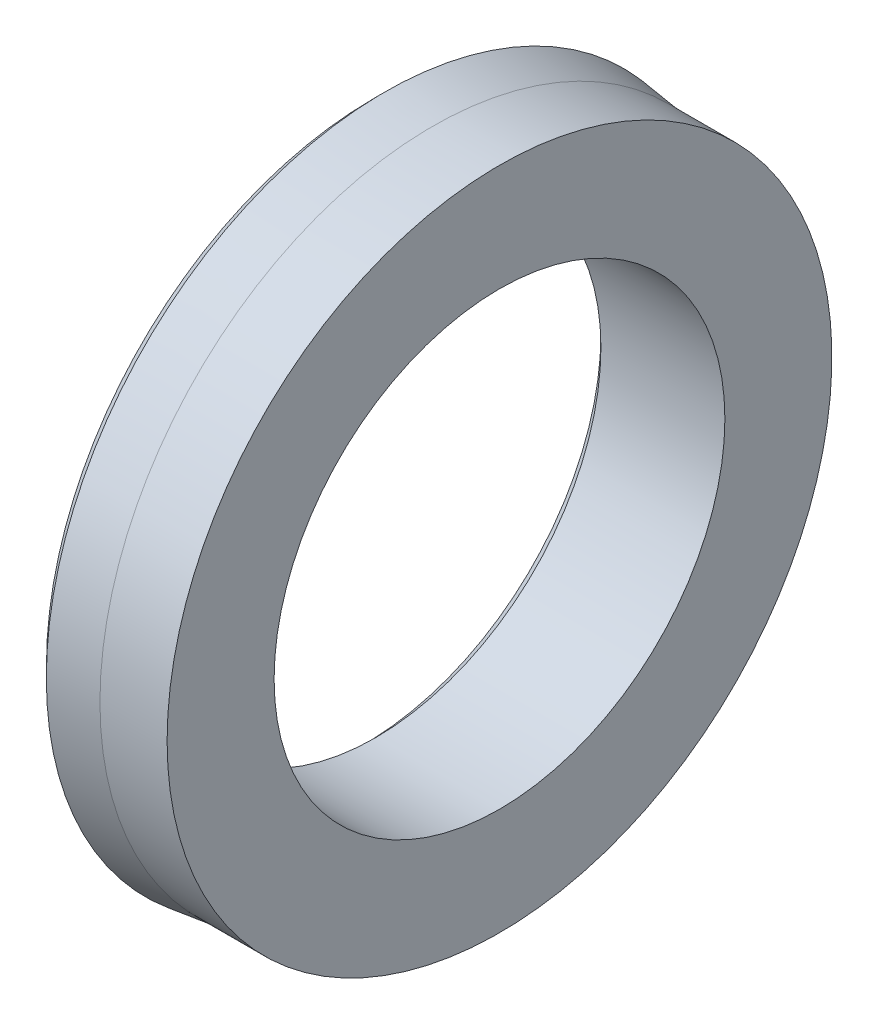
SolidWorks part; units mm, degrees
material "EPDM 60 Durometer"
ref_plane "Front" through (0, 0, 0) normal (0, 0, 1) x (1, 0, 0)
ref_plane "Top" through (0, 0, 0) normal (0, 1, 0) x (1, 0, 0)
ref_plane "Right" through (0, 0, 0) normal (1, 0, 0) x (0, 0, -1)
ref_axis "Axis1" through (-84.4107, 0, 0) along (1, 0, 0)
ref_axis "Axis2" through (0, 64.3378, 0) along (0, -1, 0)
ref_axis "Axis3" through (0, 0, -102.329) along (0, 0, 1)
sketch "Sketch1" plane through (0, 0, 0) normal (0, 0, 1) x (1, 0, 0)
  line L0 (0, 0) -> (16.5173, 0) construction
  line L1 (2.9839, 24) -> (2.9839, 21)
  line L2 (2.9839, 21) -> (3.9839, 20)
  line L3 (3.9839, 20) -> (14.9839, 20)
  line L4 (14.9839, 20) -> (14.9839, 29.495)
  line L5 (14.9839, 29.495) -> (9.0239, 29.495)
  line L6 (9.0239, 29.495) -> (4.7839, 30.0149)
  line L7 (4.7839, 30.0149) -> (3.7839, 29)
  line L8 (3.7839, 29) -> (3.7839, 26.2457)
  line L9 (3.7839, 26.2457) -> (7.4639, 25.7945)
  line L11 (7.4639, 24) -> (2.9839, 24)
  arc A0 (7.4639, 24) -> (7.4639, 25.7945) centre (7.4639, 24.8973) ccw
  dimension "D1" = 20
  dimension "D2" = 29.495
  dimension "D3" = 5.96
  dimension "D4" = 10.2
  dimension "D5" = 11.2
  dimension "D6" = 6.99
  dimension "D8" = 6.99
  dimension "D9" = 12
  dimension "D10" = 11
  dimension "D11" = 135
  dimension "D12" = 24
  dimension "D13" = 29
revolve "Revolve1" add sketch "Sketch1" angle 360 about L0
ref_plane "Plane1" through (14.9839, 0, 0) normal (1, 0, 0) x (0, 0, -1)
